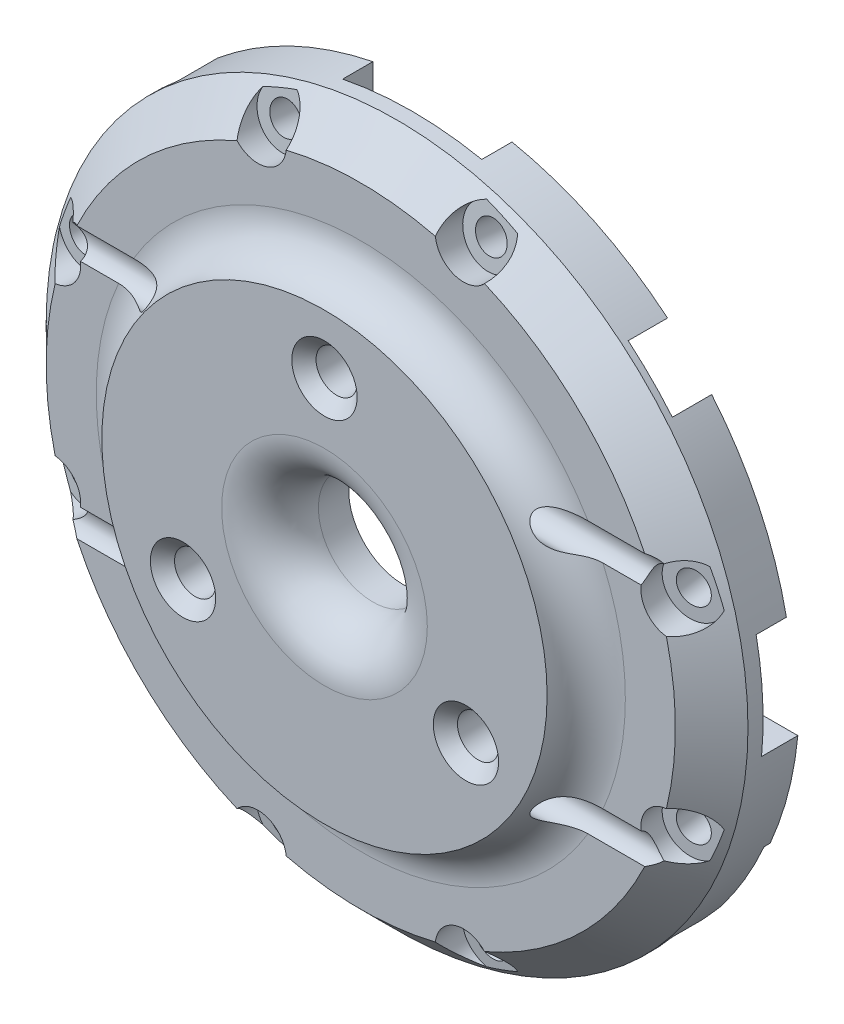
SolidWorks part; units mm, degrees
ref_plane "Front Plane" through (0, 0, 0) normal (0, 0, 1) x (1, 0, 0)
ref_plane "Top Plane" through (0, 0, 0) normal (0, 1, 0) x (1, 0, 0)
ref_plane "Right Plane" through (0, 0, 0) normal (1, 0, 0) x (0, 0, -1)
sketch "Sketch1" plane through (0, 0, 0) normal (0, 0, 1) x (1, 0, 0)
  circle A0 centre (0, 0) radius 29
  dimension "D1" = 58
extrude "Boss-Extrude1" add sketch "Sketch1" along normal blind 6.75
sketch "Sketch3" plane through (0, 0, 0) normal (0, 0, -1) x (-1, 0, 0)
  line L1 (-22.25, -22.25) -> (22.25, -22.25)
  line L2 (-22.25, -22.25) -> (-22.25, 22.25)
  line L3 (-22.25, 22.25) -> (22.25, 22.25)
  line L4 (22.25, -22.25) -> (22.25, 22.25)
  line L5 (-22.25, -22.25) -> (22.25, 22.25) construction
  line L6 (-22.25, 22.25) -> (22.25, -22.25) construction
  point P0 (0, 0)
  dimension "D1" = 44.5
extrude "Cut-Extrude1" cut sketch "Sketch3" against normal blind 3.25
sketch "Sketch4" plane through (0, 0, 6.75) normal (0, 0, 1) x (1, 0, 0)
  circle A0 centre (0, 0) radius 18.4
  dimension "D1" = 36.8
extrude "Boss-Extrude2" add sketch "Sketch4" along normal blind 3
fillet "Fillet1" radius 3.5 1 edges at (18.4, 0, 6.75)
sketch "Sketch5" plane through (0, 0, 9.75) normal (0, 0, 1) x (1, 0, 0)
  line L0 (-11.6913, -6.75) -> (0, 13.5) construction
  line L1 (0, 13.5) -> (11.6913, -6.75) construction
  line L2 (11.6913, -6.75) -> (-11.6913, -6.75) construction
  circle A2 centre (0, 0) radius 13.5 construction
  circle A3 centre (0, 13.5) radius 1.7
  circle A4 centre (11.6913, -6.75) radius 1.7
  circle A5 centre (-11.6913, -6.75) radius 1.7
  dimension "D1" = 3.4
  dimension "D2" = 27
extrude "Cut-Extrude2" cut sketch "Sketch5" against normal through all
sketch "Sketch7" plane through (0, 0, 3.25) normal (0, 0, -1) x (-1, 0, 0)
  circle A0 centre (-11.6913, -6.75) radius 3.25
  circle A1 centre (11.6913, -6.75) radius 3.25
  circle A2 centre (0, 13.5) radius 3.25
  dimension "D1" = 6.5
extrude "Cut-Extrude3" cut sketch "Sketch7" against normal blind 2
chamfer "Chamfer2" distance 3 angle 45 1 edges at (29, 0, 6.75)
sketch "Sketch9" plane through (0, 0, 0) normal (1, 0, 0) x (0, 0, -1)
  line L0 (-26.5723, 0) -> (15.7273, 0) construction
  line L2 (-6.75, 21.8641) -> (-6.75, -21.8641) construction
  circle A0 centre (-7.25, 10) radius 1.3
  circle A1 centre (-7.25, -10) radius 1.3
  dimension "D1" = 2.6
  dimension "D2" = 20
  dimension "D3" = 0.5
extrude "Cut-Extrude5" cut sketch "Sketch9" against normal through all both and the other way through all
sketch "Sketch10" plane through (0, 0, 0) normal (0, 0, -1) x (-1, 0, 0)
  line L0 (5.75, -22.0007) -> (5.75, -34.0342)
  line L1 (22.0007, 5.75) -> (34.0342, 5.75)
  line L2 (22.0007, 5.75) -> (22.0007, -5.75)
  line L3 (22.0007, -5.75) -> (34.0342, -5.75)
  line L4 (34.0342, 5.75) -> (34.0342, -5.75)
  line L5 (5.75, -22.0007) -> (-5.75, -22.0007)
  line L6 (-5.75, -22.0007) -> (-5.75, -34.0342)
  line L7 (5.75, -34.0342) -> (-5.75, -34.0342)
  line L8 (-22.0007, -5.75) -> (-34.0342, -5.75)
  line L9 (-22.0007, -5.75) -> (-22.0007, 5.75)
  line L10 (-22.0007, 5.75) -> (-34.0342, 5.75)
  line L11 (-34.0342, -5.75) -> (-34.0342, 5.75)
  line L12 (-5.75, 22.0007) -> (-5.75, 34.0342)
  line L13 (-5.75, 22.0007) -> (5.75, 22.0007)
  line L14 (5.75, 22.0007) -> (5.75, 34.0342)
  line L15 (-5.75, 34.0342) -> (5.75, 34.0342)
  point P4 (22.0007, 0)
  point P21 (0, 0)
  dimension "D1" = 11.5
  dimension "D2" = 4
extrude "Cut-Extrude6" cut sketch "Sketch10" against normal blind 2.5
sketch "Sketch13" plane through (0, 0, 3.25) normal (0, 0, -1) x (-1, 0, 0)
  line L0 (-22.25, 18.5994) -> (-22.25, -18.5994) construction
  line L1 (-22.15, 14.75) -> (-15.65, 14.75)
  line L2 (-22.15, 14.75) -> (-22.15, 8.25)
  line L3 (-22.15, 8.25) -> (-15.65, 8.25)
  line L4 (-15.65, 14.75) -> (-15.65, 8.25)
  line L5 (18.5994, 22.25) -> (-18.5994, 22.25) construction
  line L6 (14.75, 22.15) -> (14.75, 15.65)
  line L7 (14.75, 22.15) -> (8.25, 22.15)
  line L8 (8.25, 22.15) -> (8.25, 15.65)
  line L9 (14.75, 15.65) -> (8.25, 15.65)
  line L10 (22.15, -14.75) -> (15.65, -14.75)
  line L11 (22.15, -14.75) -> (22.15, -8.25)
  line L12 (22.15, -8.25) -> (15.65, -8.25)
  line L13 (15.65, -14.75) -> (15.65, -8.25)
  line L14 (-14.75, -22.15) -> (-14.75, -15.65)
  line L15 (-14.75, -22.15) -> (-8.25, -22.15)
  line L16 (-8.25, -22.15) -> (-8.25, -15.65)
  line L17 (-14.75, -15.65) -> (-8.25, -15.65)
  point P23 (0, 0)
  dimension "D1" = 0.1
  dimension "D2" = 7.5
  dimension "D4" = 6.5
  dimension "D3" = 4
extrude "Cut-Extrude9" cut sketch "Sketch13" against normal blind 2.25
chamfer "Chamfer5" distance 1 angle 45 12 edges at (-14.75, 18.9, 3.25) (-11.5, 15.65, 3.25) (-8.25, 18.9, 3.25) (14.75, -18.9, 3.25) (11.5, -15.65, 3.25) (8.25, -18.9, 3.25) (-18.9, -8.25, 3.25) (-15.65, -11.5, 3.25) (-18.9, -14.75, 3.25) (18.9, 8.25, 3.25) (15.65, 11.5, 3.25) (18.9, 14.75, 3.25)
sketch "Sketch14" plane through (0, 0, 0) normal (0, 0, -1) x (-1, 0, 0)
  line L1 (-35.1198, 0) -> (-19.2322, 0)
  line L2 (-35.1198, 0) -> (-35.1198, -11.6)
  line L3 (-35.1198, -11.6) -> (-19.2322, -11.6)
  line L4 (-19.2322, 0) -> (-19.2322, -11.6)
  dimension "D1" = 11.6
extrude "Cut-Extrude10" cut sketch "Sketch14" against normal up to surface (2.5 mm away) up to face at (25.4811, 0, 2.5)
fillet "Fillet2" radius 1.5 3 edges at (-8.5776, -5.8189, 3.25) (8.4413, -6.75, 3.25) (-3.25, 13.5, 3.25)
sketch "Sketch15" plane through (0, 0, 6.75) normal (0, 0, 1) x (1, 0, 0)
  line L0 (0, 0) -> (11.6673, 11.6673) construction
  line L1 (0, 0) -> (36.7921, 0) construction
  circle A0 centre (11.6673, 11.6673) radius 12.5
  circle A1 centre (0, 0) radius 29 construction
  dimension "D2" = 25
  dimension "D1" = 45
sketch "Sketch19" plane through (0, 0, 2.5) normal (0, 0, -1) x (-1, 0, 0)
  line L0 (-22.25, -2.75) -> (-22.25, -11.6)
  line L1 (-22.25, -11.6) -> (-22.25, 5.75) construction
  line L2 (-22.25, -11.6) -> (-26.5789, -11.6)
  line L3 (-22.25, -2.75) -> (-28.8693, -2.75)
  line L4 (-22.25, 5.75) -> (-28.4242, 5.75) construction
  arc A0 (-28.8693, -2.75) -> (-26.5789, -11.6) centre (0, 0) ccw
  arc A1 (-28.4242, 5.75) -> (-26.5789, -11.6) centre (0, 0) ccw construction
  dimension "D1" = 8.5
extrude "Boss-Extrude3" add sketch "Sketch19" along normal blind 3
chamfer "Chamfer7" distance 1.25 angle 45 1 edges at (22.25, -7.175, -0.5)
sketch "Sketch16" plane through (0, 0, 9.75) normal (0, 0, 1) x (1, 0, 0)
  circle A0 centre (0, 0) radius 4.5
  dimension "D1" = 9
extrude "Cut-Extrude11" cut sketch "Sketch16" against normal through all
fillet "Fillet3" radius 4 1 edges at (4.5, 0, 9.75)
chamfer "Chamfer6" distance 1 angle 45 3 edges at (13.3913, -6.75, 9.75) (-9.9913, -6.75, 9.75) (1.7, 13.5, 9.75)
ref_axis "Axis1" through (0, 0, -0.4875) along (0, 0, 1)
ref_axis "Axis2" through (0, 31.9, 0) along (0, -1, 0)
ref_plane "Plane1" through (0, 0, 0) normal (0.1219, 0, 0.9925) x (0, -1, 0)
sketch "Sketch17" plane through (0, 0, 0) normal (0.1219, 0, 0.9925) x (0, -1, 0)
  line L0 (0, 0) -> (0, 33.2124) construction
  line L1 (0, 0.0594) -> (0, -1.2476) construction
  circle A0 centre (-8.5, 24.5) radius 1.3
  circle A1 centre (8.5, 24.5) radius 1.3
  dimension "D1" = 2.6
  dimension "D2" = 17
  dimension "D3" = 24.5
extrude "Cut-Extrude12" cut sketch "Sketch17" along normal through all
sketch "Sketch18" plane through (0, 0, 0) normal (0.1219, 0, 0.9925) x (0, -1, 0)
  circle A0 centre (-8.5, 24.5) radius 2.35
  circle A1 centre (8.5, 24.5) radius 2.35
  dimension "D1" = 4.7
extrude "Cut-Extrude13" cut sketch "Sketch18" against normal blind 12.5 from offset 20
pattern_circular "CirPattern1" count 4 over 360 about axis through (0, 0, -0.4875) along (0, 0, 1) of "Cut-Extrude12", "Cut-Extrude13"
